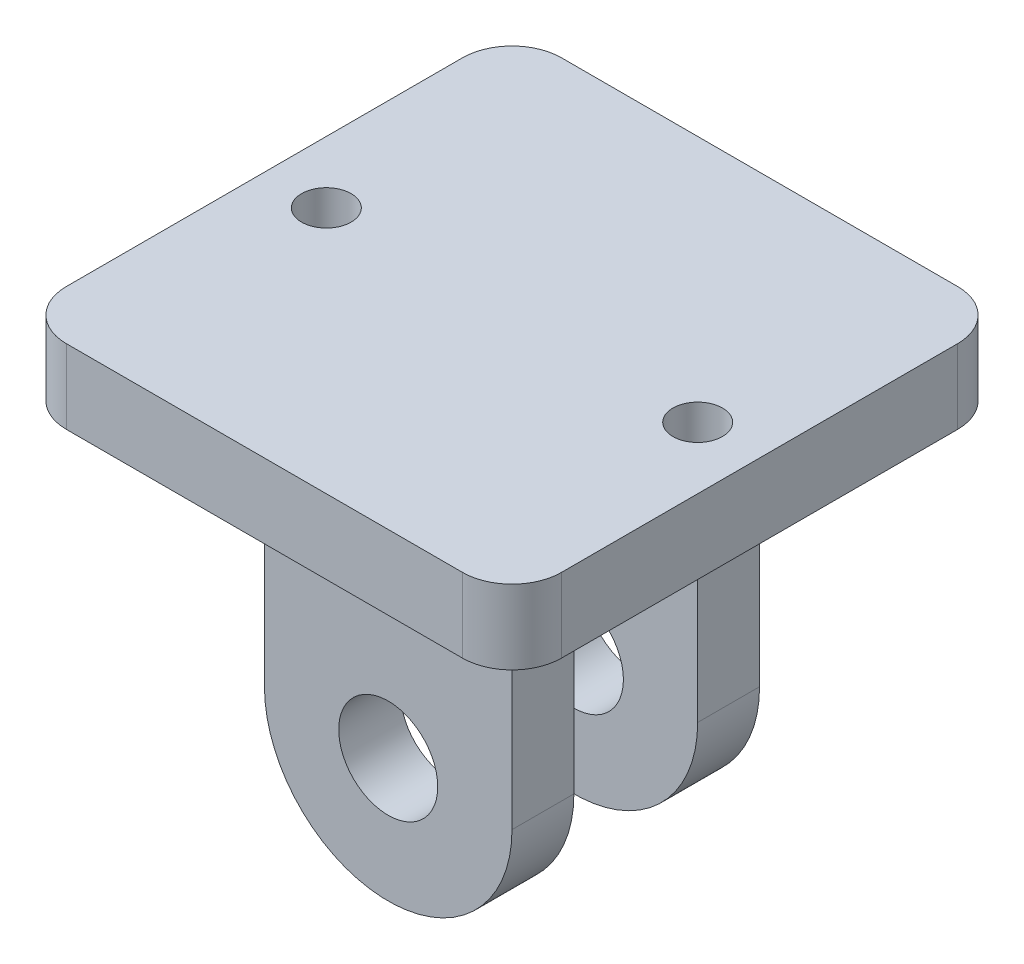
SolidWorks part; units mm, degrees
ref_plane "Plan de face" through (0, 0, 0) normal (0, 0, 1) x (1, 0, 0)
ref_plane "Plan de dessus" through (0, 0, 0) normal (0, 1, 0) x (1, 0, 0)
ref_plane "Plan de droite" through (0, 0, 0) normal (1, 0, 0) x (0, 0, -1)
sketch "Esquisse1" plane through (0, 0, 0) normal (0, 0, 1) x (1, 0, 0)
  line L1 (-5, 7.5) -> (5, 7.5)
  line L2 (-5, 7.5) -> (-5, -7.5)
  line L3 (-5, -7.5) -> (5, -7.5)
  line L4 (5, 7.5) -> (5, -7.5)
  line L5 (-5, 7.5) -> (5, -7.5) construction
  line L6 (-5, -7.5) -> (5, 7.5) construction
  point P0 (0, 0)
  dimension "D1" = 10
  dimension "D2" = 15
extrude "Boss.-Extru.1" add sketch "Esquisse1" along normal blind 10
fillet "Congé1" 2 edges at (-5, -7.5, 5) (5, -7.5, 5) type full round first side face at (-5, 0, 5) second side face at (5, 0, 5) middle face at (0, -7.5, 5)
sketch "Esquisse3" plane through (-5, 0, 0) normal (-1, 0, 0) x (0, 0, 1)
  line L0 (5, 7.5) -> (5, -7.5) construction
  line L1 (10, 7.5) -> (0, 7.5) construction
  line L2 (0, -7.5) -> (10, -7.5) construction
  line L4 (2.5, 4.5) -> (7.5, 4.5)
  line L5 (2.5, 4.5) -> (2.5, -7.5)
  line L6 (2.5, -7.5) -> (7.5, -7.5)
  line L7 (7.5, 4.5) -> (7.5, -7.5)
  line L8 (2.5, 4.5) -> (7.5, -7.5) construction
  line L9 (2.5, -7.5) -> (7.5, 4.5) construction
  point P6 (5, -1.5)
  dimension "D1" = 3
  dimension "D2" = 5
extrude "Enlèv. mat.-Extru.1" cut sketch "Esquisse3" against normal blind 10
sketch "Esquisse4" plane through (0, 7.5, 0) normal (0, 1, 0) x (1, 0, 0)
  line L0 (8, 5) -> (-8, 5)
  line L1 (-10, 3) -> (-10, -13)
  line L2 (-8, -15) -> (8, -15)
  line L3 (10, -13) -> (10, 3)
  line L4 (5, 0) -> (-5, 0)
  line L5 (-5, 0) -> (-5, -10)
  line L6 (-5, -10) -> (5, -10)
  line L7 (5, -10) -> (5, 0)
  line L8 (5, 0) -> (-5, 0)
  line L9 (-5, 0) -> (-5, -10)
  line L10 (-5, -10) -> (5, -10)
  line L11 (5, -10) -> (5, 0)
  line L12 (10, 5) -> (-10, 5) construction
  line L13 (10, -15) -> (10, 5) construction
  line L14 (-10, -15) -> (10, -15) construction
  line L15 (-10, 5) -> (-10, -15) construction
  arc A0 (8, 5) -> (10, 3) centre (8, 3) cw
  arc A1 (8, -15) -> (10, -13) centre (8, -13) ccw
  arc A2 (-10, -13) -> (-8, -15) centre (-8, -13) ccw
  arc A3 (-8, 5) -> (-10, 3) centre (-8, 3) ccw
  line M13 (5, 0) -> (-5, 0)
  line M14 (-5, 0) -> (-5, -10)
  line M15 (-5, -10) -> (5, -10)
  line M16 (5, -10) -> (5, 0)
  dimension "D3" = 2
  dimension "D1" = 0
  dimension "D2" = 5
extrude "Boss.-Extru.2" add sketch "Esquisse4" along normal blind 3 contours M16 M13 M14 M15 | L0 A3 L1 A2 L2 A1 L3 A0 M13 M16 M15 M14 region at (9.2142, 7.5, -4.2142) region at (0, 7.5, 5)
sketch "Esquisse5" plane through (0, 7.5, 0) normal (0, -1, 0) x (1, 0, 0)
  line L0 (-10, 5) -> (-5, 5) construction
  line L1 (-10, -3) -> (-10, 13) construction
  line L2 (10, 13) -> (10, -3) construction
  line L7 (5, 5) -> (10, 5) construction
  circle A0 centre (-7.5, 5) radius 1
  circle A1 centre (7.5, 5) radius 1
  dimension "D1" = 2
  dimension "D2" = 2
extrude "Enlèv. mat.-Extru.2" cut sketch "Esquisse5" against normal blind 3
sketch "Esquisse6" plane through (0, 0, 10) normal (0, 0, 1) x (1, 0, 0)
  circle A0 centre (0, -2.5) radius 2
  arc A1 (-5, -2.5) -> (5, -2.5) centre (0, -2.5) ccw construction
  arc A3 (-5, -2.5) -> (5, -2.5) centre (0, -2.5) ccw
  dimension "4." = 4
extrude "Enlèv. mat.-Extru.3" cut sketch "Esquisse6" against normal through all contours A0 region at (0, -2.5, 10)
